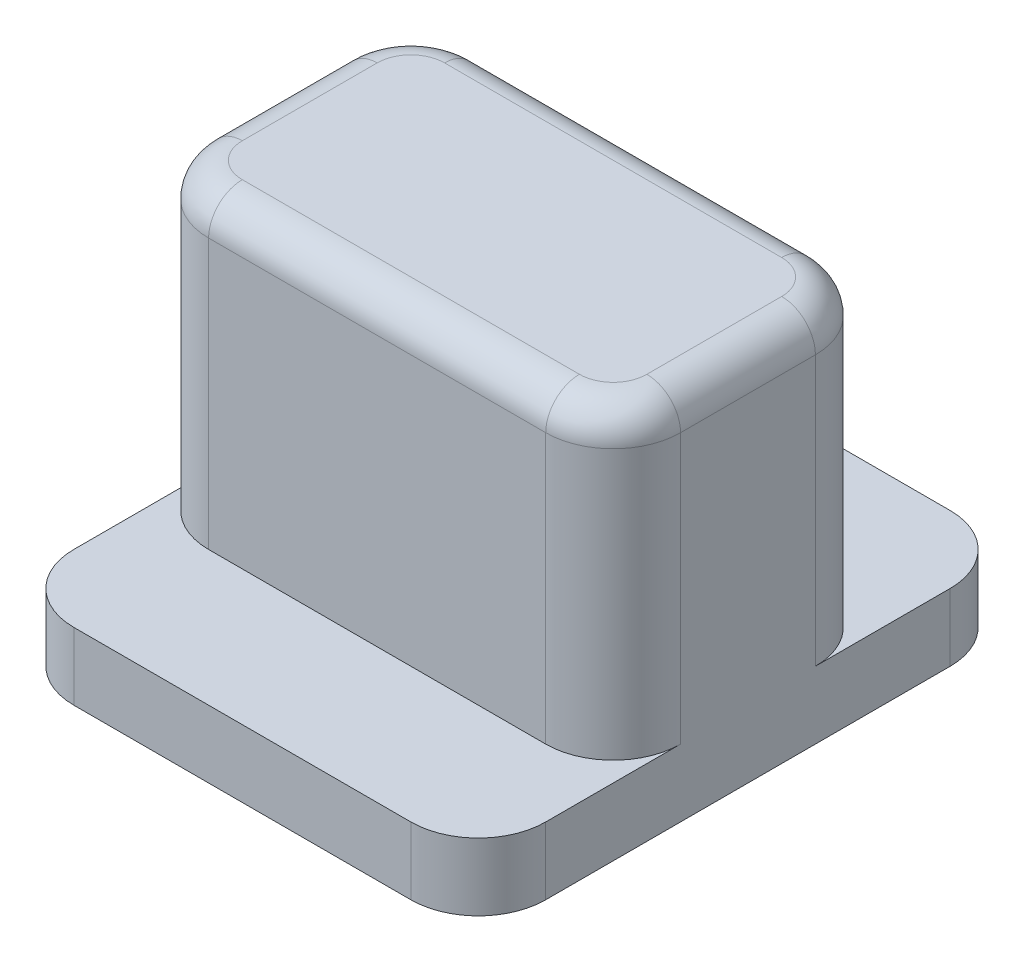
SolidWorks part; units mm, degrees
ref_plane "Front Plane" through (0, 0, 0) normal (0, 0, 1) x (1, 0, 0)
ref_plane "Top Plane" through (0, 0, 0) normal (0, 1, 0) x (1, 0, 0)
ref_plane "Right Plane" through (0, 0, 0) normal (1, 0, 0) x (0, 0, -1)
sketch "草图1" plane through (0, 0, 0) normal (0, 1, 0) x (1, 0, 0)
  line L4 (26.5529, 0.5) -> (33.5529, 0.5)
  line L5 (33.5529, 0.5) -> (33.5529, 8.5)
  line L6 (33.5529, 8.5) -> (26.5529, 8.5)
  line L7 (26.5529, 8.5) -> (26.5529, 0.5)
extrude "凸台-拉伸1" add sketch "草图1" along normal blind 1
sketch "草图2" plane through (0, 1, 0) normal (0, 1, 0) x (1, 0, 0)
  line L0 (26.5529, 4.5) -> (26.5529, 6.5)
  line L1 (26.5529, 8.5) -> (26.5529, 0.5) construction
  line L2 (26.5529, 6.5) -> (33.5529, 6.5)
  line L3 (33.5529, 0.5) -> (33.5529, 8.5) construction
  line L4 (33.5529, 6.5) -> (33.5529, 2.5)
  line L5 (33.5529, 2.5) -> (26.5529, 2.5)
  line L6 (26.5529, 2.5) -> (26.5529, 4.5)
extrude "凸台-拉伸2" add sketch "草图2" along normal blind 4.5
fillet "圆角1" radius 1 8 edges at (26.5529, 0.5, -8.5) (26.5529, 3.25, -6.5) (26.5529, 3.25, -2.5) (33.5529, 3.25, -2.5) (33.5529, 3.25, -6.5) (33.5529, 0.5, -8.5) (26.5529, 0.5, -0.5) (33.5529, 0.5, -0.5)
fillet "圆角2" radius 0.5 8 edges at (33.26, 5.5, -6.2071) (33.5529, 5.5, -4.5) (33.26, 5.5, -2.7929) (30.0529, 5.5, -2.5) (26.8458, 5.5, -2.7929) (26.5529, 5.5, -4.5) (26.8458, 5.5, -6.2071) (30.0529, 5.5, -6.5)
